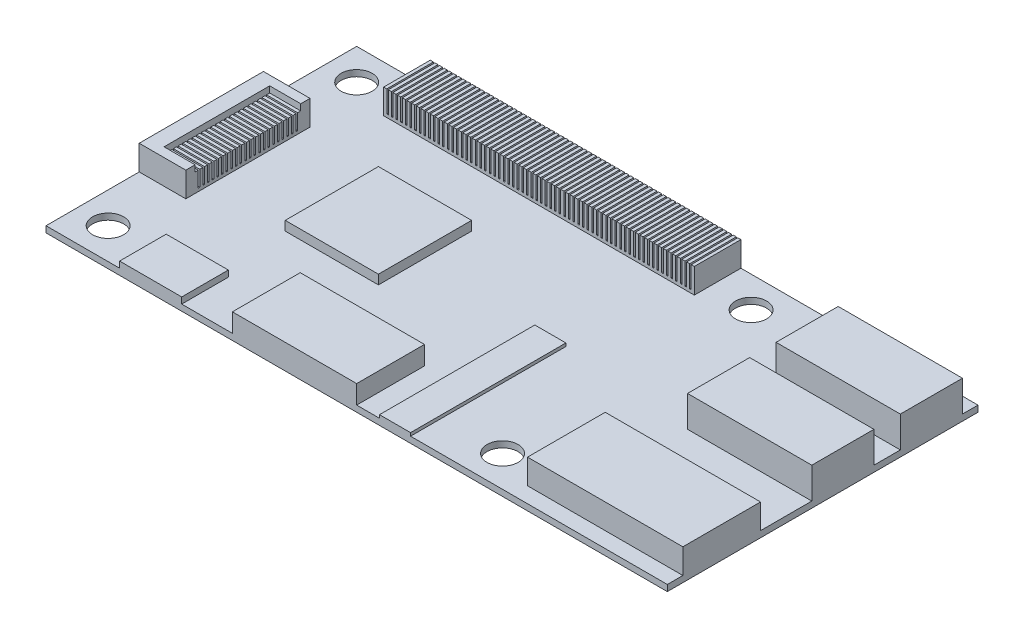
SolidWorks part; units mm, degrees
ref_plane "Front Plane" through (0, 0, 0) normal (0, 0, 1) x (1, 0, 0)
ref_plane "Top Plane" through (0, 0, 0) normal (0, 1, 0) x (1, 0, 0)
ref_plane "Right Plane" through (0, 0, 0) normal (1, 0, 0) x (0, 0, -1)
sketch "Sketch1" plane through (0, 0, 0) normal (0, 1, 0) x (1, 0, 0)
  line L1 (-10, -5) -> (10, -5)
  line L2 (-10, -5) -> (-10, 5)
  line L3 (-10, 5) -> (10, 5)
  line L4 (10, -5) -> (10, 5)
  line L5 (-10, -5) -> (10, 5) construction
  line L6 (-10, 5) -> (10, -5) construction
  line L7 (-10, 2) -> (-8.5, 2)
  line L8 (-10, 2) -> (-10, -2)
  line L9 (-10, -2) -> (-8.5, -2)
  line L10 (-8.5, 2) -> (-8.5, -2)
  line L11 (-7.631, 5) -> (2.369, 5)
  line L12 (-7.631, 5) -> (-7.631, 3.5)
  line L13 (-7.631, 3.5) -> (2.369, 3.5)
  line L14 (2.369, 5) -> (2.369, 3.5)
  line L15 (10, 4.5) -> (6, 4.5)
  line L16 (10, 4.5) -> (10, 2.5)
  line L17 (10, 2.5) -> (6, 2.5)
  line L18 (6, 4.5) -> (6, 2.5)
  line L19 (10, 1.65) -> (6, 1.65)
  line L20 (10, 1.65) -> (10, -0.35)
  line L21 (10, -0.35) -> (6, -0.35)
  line L22 (6, 1.65) -> (6, -0.35)
  line L23 (10, -2) -> (5, -2)
  line L24 (10, -2) -> (10, -4.5)
  line L25 (10, -4.5) -> (5, -4.5)
  line L26 (5, -2) -> (5, -4.5)
  line L27 (-7.631, -5) -> (-5.631, -5)
  line L28 (-7.631, -5) -> (-7.631, -3.5)
  line L29 (-7.631, -3.5) -> (-5.631, -3.5)
  line L30 (-5.631, -5) -> (-5.631, -3.5)
  line L31 (-4, -5) -> (0, -5)
  line L32 (-4, -5) -> (-4, -2.8173)
  line L33 (-4, -2.8173) -> (0, -2.8173)
  line L34 (0, -5) -> (0, -2.8173)
  line L35 (0.7346, -5) -> (1.7346, -5)
  line L36 (0.7346, -5) -> (0.7346, 0)
  line L37 (0.7346, 0) -> (1.7346, 0)
  line L38 (1.7346, -5) -> (1.7346, 0)
  line L40 (-7.481, 5) -> (-7.381, 5)
  line L42 (-7.481, 3.5) -> (-7.381, 3.5)
  circle A0 centre (-9, -4) radius 1
  circle A1 centre (-9, 4) radius 1
  circle A2 centre (3.6952, 4) radius 1
  circle A3 centre (3.6952, -4) radius 1
  circle A4 centre (-9, -4) radius 0.5
  circle A5 centre (-9, 4) radius 0.5
  circle A6 centre (3.6952, 4) radius 0.5
  circle A7 centre (3.6952, -4) radius 0.5
  point P0 (0, 0)
  dimension "D3" = 2
  dimension "D4" = 2
  dimension "D10" = 2
  dimension "D25" = 2
  dimension "D27" = 1
  dimension "D28" = 1
  dimension "D29" = 1
  dimension "D30" = 1
  dimension "D1" = 10
  dimension "D2" = 20
  dimension "D5" = 4
  dimension "D6" = 1.5
  dimension "D7" = 3
  dimension "D8" = 10
  dimension "D9" = 1.5
  dimension "D11" = 0.5
  dimension "D12" = 4
  dimension "D13" = 2
  dimension "D14" = 4
  dimension "D15" = 2
  dimension "D16" = 0.85
  dimension "D17" = 5
  dimension "D18" = 2.5
  dimension "D19" = 0.5
  dimension "D20" = 2
  dimension "D21" = 1.5
  dimension "D22" = 6
  dimension "D23" = 4
  dimension "D24" = 1
  dimension "D26" = 5
  dimension "D32" = 0.1
extrude "Boss-Extrude10" add sketch "Sketch1" against normal blind 0.2 contours L1 A3 L4 L25 L26 L23 L21 L22 L19 L17 L18 L15 L3 A2 L14 L13 L12 A1 L2 L7 L10 L9 A0 L28 L29 L30 L32 L33 L34 L36 L37 L38 | L14 L3 L12 L13 | L1 L34 L33 L32 | L1 L38 L37 L36 | L1 L30 L29 L28 | L10 L7 L2 L9 | L23 L26 L25 L4 | L19 L22 L21 L4 | L15 L18 L17 L4 | A0 L2 L1 | A1 L3 L2 | A0 | A1 | A2 | A3 region at (-6.631, 0, 4.25) region at (3.0081, 0, 3.3129) region at (4.3823, 0, -4.6871) region at (-0.4809, 0, -0.0253) region at (-9.7766, 0, 4.7766) region at (-9.6871, 0, 4.6871) region at (-2, 0, 3.9086) region at (-9.25, 0, 0) region at (1.2346, 0, 2.5) region at (-9.7766, 0, -4.7766) region at (-9.6871, 0, -4.6871) region at (-2.631, 0, -4.25) region at (7.5, 0, 3.25) region at (8, 0, -0.65) region at (8, 0, -3.5)
extrude "Boss-Extrude11" add sketch "Sketch1<5>" along normal blind 1 contours L15 L18 L17 L4 | L19 L22 L21 L4 region at (8, 0, -0.65) region at (8, 0, -3.5)
sketch "Sketch1<5>" plane through (0, 0, 0) normal (0, 1, 0) x (1, 0, 0) same geometry as "Sketch1"
extrude "Boss-Extrude12" add sketch "Sketch1<6>" along normal blind 0.8 contours L23 L26 L25 L4 region at (7.5, 0, 3.25)
sketch "Sketch1<6>" plane through (0, 0, 0) normal (0, 1, 0) x (1, 0, 0) same geometry as "Sketch1"
extrude "Boss-Extrude13" add sketch "Sketch1<7>" along normal blind 0.1 contours L14 L3 L12 L13 | L10 L7 L2 L9 | L1 L38 L37 L36 region at (-9.25, 0, 0) region at (1.2346, 0, 2.5) region at (-2.631, 0, -4.25)
sketch "Sketch1<7>" plane through (0, 0, 0) normal (0, 1, 0) x (1, 0, 0) same geometry as "Sketch1"
extrude "Boss-Extrude14" add sketch "Sketch1<8>" along normal blind 0.2 contours L1 L30 L29 L28 region at (-6.631, 0, 4.25)
sketch "Sketch1<8>" plane through (0, 0, 0) normal (0, 1, 0) x (1, 0, 0) same geometry as "Sketch1"
extrude "Boss-Extrude15" add sketch "Sketch1<9>" along normal blind 0.6 contours L1 L34 L33 L32 region at (-2, 0, 3.9086)
sketch "Sketch1<9>" plane through (0, 0, 0) normal (0, 1, 0) x (1, 0, 0) same geometry as "Sketch1"
sketch "Sketch3" plane through (0, 0.1, 0) normal (0, 1, 0) x (1, 0, 0)
  line L0 (-7.631, 3.5) -> (2.369, 3.5) construction
  line L1 (-7.631, 5) -> (-7.531, 5)
  line L2 (-7.631, 5) -> (-7.631, 3.5)
  line L3 (-7.631, 3.5) -> (-7.531, 3.5)
  line L4 (-7.531, 5) -> (-7.531, 3.5)
  line L5 (-7.631, 5) -> (2.369, 5) construction
  line L6 (-7.481, 5) -> (-7.381, 5)
  line L7 (-7.481, 5) -> (-7.481, 3.5)
  line L8 (-7.481, 3.5) -> (-7.381, 3.5)
  line L9 (-7.381, 5) -> (-7.381, 3.5)
  line L10 (-7.331, 5) -> (-7.331, 3.5)
  line L11 (-7.231, 5) -> (-7.231, 3.5)
  line L12 (-7.181, 5) -> (-7.181, 3.5)
  line L13 (-7.081, 5) -> (-7.081, 3.5)
  line L14 (-7.031, 5) -> (-7.031, 3.5)
  line L15 (-6.931, 5) -> (-6.931, 3.5)
  line L16 (-6.881, 5) -> (-6.881, 3.5)
  line L17 (-6.781, 5) -> (-6.781, 3.5)
  line L18 (-6.731, 5) -> (-6.731, 3.5)
  line L19 (-6.631, 5) -> (-6.631, 3.5)
  line L20 (-6.581, 5) -> (-6.581, 3.5)
  line L21 (-6.481, 5) -> (-6.481, 3.5)
  line L22 (-6.431, 5) -> (-6.431, 3.5)
  line L23 (-6.331, 5) -> (-6.331, 3.5)
  line L24 (-6.281, 5) -> (-6.281, 3.5)
  line L25 (-6.181, 5) -> (-6.181, 3.5)
  line L26 (-6.131, 5) -> (-6.131, 3.5)
  line L27 (-6.031, 5) -> (-6.031, 3.5)
  line L28 (-5.981, 5) -> (-5.981, 3.5)
  line L29 (-5.881, 5) -> (-5.881, 3.5)
  line L30 (-5.831, 5) -> (-5.831, 3.5)
  line L31 (-5.731, 5) -> (-5.731, 3.5)
  line L32 (-5.681, 5) -> (-5.681, 3.5)
  line L33 (-5.581, 5) -> (-5.581, 3.5)
  line L34 (-5.531, 5) -> (-5.531, 3.5)
  line L35 (-5.431, 5) -> (-5.431, 3.5)
  line L36 (-5.381, 5) -> (-5.381, 3.5)
  line L37 (-5.281, 5) -> (-5.281, 3.5)
  line L38 (-5.231, 5) -> (-5.231, 3.5)
  line L39 (-5.131, 5) -> (-5.131, 3.5)
  line L40 (-5.081, 5) -> (-5.081, 3.5)
  line L41 (-4.981, 5) -> (-4.981, 3.5)
  line L42 (-4.931, 5) -> (-4.931, 3.5)
  line L43 (-4.831, 5) -> (-4.831, 3.5)
  line L44 (-4.781, 5) -> (-4.781, 3.5)
  line L45 (-4.681, 5) -> (-4.681, 3.5)
  line L46 (-4.631, 5) -> (-4.631, 3.5)
  line L47 (-4.531, 5) -> (-4.531, 3.5)
  line L48 (-4.481, 5) -> (-4.481, 3.5)
  line L49 (-4.381, 5) -> (-4.381, 3.5)
  line L50 (-4.331, 5) -> (-4.331, 3.5)
  line L51 (-4.231, 5) -> (-4.231, 3.5)
  line L52 (-4.181, 5) -> (-4.181, 3.5)
  line L53 (-4.081, 5) -> (-4.081, 3.5)
  line L54 (-4.031, 5) -> (-4.031, 3.5)
  line L55 (-3.931, 5) -> (-3.931, 3.5)
  line L56 (-3.881, 5) -> (-3.881, 3.5)
  line L57 (-3.781, 5) -> (-3.781, 3.5)
  line L58 (-3.731, 5) -> (-3.731, 3.5)
  line L59 (-3.631, 5) -> (-3.631, 3.5)
  line L60 (-3.581, 5) -> (-3.581, 3.5)
  line L61 (-3.481, 5) -> (-3.481, 3.5)
  line L62 (-3.431, 5) -> (-3.431, 3.5)
  line L63 (-3.331, 5) -> (-3.331, 3.5)
  line L64 (-3.281, 5) -> (-3.281, 3.5)
  line L65 (-3.181, 5) -> (-3.181, 3.5)
  line L66 (-3.131, 5) -> (-3.131, 3.5)
  line L67 (-3.031, 5) -> (-3.031, 3.5)
  line L68 (-2.981, 5) -> (-2.981, 3.5)
  line L69 (-2.881, 5) -> (-2.881, 3.5)
  line L70 (-2.831, 5) -> (-2.831, 3.5)
  line L71 (-2.731, 5) -> (-2.731, 3.5)
  line L72 (-2.681, 5) -> (-2.681, 3.5)
  line L73 (-2.581, 5) -> (-2.581, 3.5)
  line L74 (-2.531, 5) -> (-2.531, 3.5)
  line L75 (-2.431, 5) -> (-2.431, 3.5)
  line L76 (-2.381, 5) -> (-2.381, 3.5)
  line L77 (-2.281, 5) -> (-2.281, 3.5)
  line L78 (-2.231, 5) -> (-2.231, 3.5)
  line L79 (-2.131, 5) -> (-2.131, 3.5)
  line L80 (-2.081, 5) -> (-2.081, 3.5)
  line L81 (-1.981, 5) -> (-1.981, 3.5)
  line L82 (-1.931, 5) -> (-1.931, 3.5)
  line L83 (-1.831, 5) -> (-1.831, 3.5)
  line L84 (-1.781, 5) -> (-1.781, 3.5)
  line L85 (-1.681, 5) -> (-1.681, 3.5)
  line L86 (-1.631, 5) -> (-1.631, 3.5)
  line L87 (-1.531, 5) -> (-1.531, 3.5)
  line L88 (-1.481, 5) -> (-1.481, 3.5)
  line L89 (-1.381, 5) -> (-1.381, 3.5)
  line L90 (-1.331, 5) -> (-1.331, 3.5)
  line L91 (-1.231, 5) -> (-1.231, 3.5)
  line L92 (-1.181, 5) -> (-1.181, 3.5)
  line L93 (-1.081, 5) -> (-1.081, 3.5)
  line L94 (-1.031, 5) -> (-1.031, 3.5)
  line L95 (-0.931, 5) -> (-0.931, 3.5)
  line L96 (-0.881, 5) -> (-0.881, 3.5)
  line L97 (-0.781, 5) -> (-0.781, 3.5)
  line L98 (-0.731, 5) -> (-0.731, 3.5)
  line L99 (-0.631, 5) -> (-0.631, 3.5)
  line L100 (-0.581, 5) -> (-0.581, 3.5)
  line L101 (-0.481, 5) -> (-0.481, 3.5)
  line L102 (-0.431, 5) -> (-0.431, 3.5)
  line L103 (-0.331, 5) -> (-0.331, 3.5)
  line L104 (-0.281, 5) -> (-0.281, 3.5)
  line L105 (-0.181, 5) -> (-0.181, 3.5)
  line L106 (-0.131, 5) -> (-0.131, 3.5)
  line L107 (-0.031, 5) -> (-0.031, 3.5)
  line L108 (0.019, 5) -> (0.019, 3.5)
  line L109 (0.119, 5) -> (0.119, 3.5)
  line L110 (0.169, 5) -> (0.169, 3.5)
  line L111 (0.269, 5) -> (0.269, 3.5)
  line L112 (0.319, 5) -> (0.319, 3.5)
  line L113 (0.419, 5) -> (0.419, 3.5)
  line L114 (0.469, 5) -> (0.469, 3.5)
  line L115 (0.569, 5) -> (0.569, 3.5)
  line L116 (0.619, 5) -> (0.619, 3.5)
  line L117 (0.719, 5) -> (0.719, 3.5)
  line L118 (0.769, 5) -> (0.769, 3.5)
  line L119 (0.869, 5) -> (0.869, 3.5)
  line L120 (0.919, 5) -> (0.919, 3.5)
  line L121 (1.019, 5) -> (1.019, 3.5)
  line L122 (1.069, 5) -> (1.069, 3.5)
  line L123 (1.169, 5) -> (1.169, 3.5)
  line L124 (1.219, 5) -> (1.219, 3.5)
  line L125 (1.319, 5) -> (1.319, 3.5)
  line L126 (1.369, 5) -> (1.369, 3.5)
  line L127 (1.469, 5) -> (1.469, 3.5)
  line L128 (1.519, 5) -> (1.519, 3.5)
  line L129 (1.619, 5) -> (1.619, 3.5)
  line L130 (1.669, 5) -> (1.669, 3.5)
  line L131 (1.769, 5) -> (1.769, 3.5)
  line L132 (1.819, 5) -> (1.819, 3.5)
  line L133 (1.919, 5) -> (1.919, 3.5)
  line L134 (1.969, 5) -> (1.969, 3.5)
  line L135 (2.069, 5) -> (2.069, 3.5)
  line L136 (2.119, 5) -> (2.119, 3.5)
  line L137 (2.219, 5) -> (2.219, 3.5)
  line L138 (2.269, 5) -> (2.269, 3.5)
  line L139 (2.369, 5) -> (2.369, 3.5)
  line M10 (2.369, 5) -> (-7.631, 5)
  line M11 (-7.631, 5) -> (-7.631, 3.5)
  line M12 (-7.631, 3.5) -> (2.369, 3.5)
  dimension "D1" = 0.1
  dimension "D2" = 0.1
  dimension "D3" = 0.05
  dimension "D4" = 66
extrude "Boss-Extrude16" add sketch "Sketch3" along normal blind 0.7 contours L4 M10 M11 M12 region at (-7.581, 0.1, -4.25)
pattern_linear "LPattern1" count 67 spacing 0.15 along (1, 0, 0) of "Boss-Extrude16"
sketch "Sketch4" plane through (0, 0.1, 0) normal (0, 1, 0) x (1, 0, 0)
  line L0 (-8.5, 1.7) -> (-9.5, 1.7)
  line L1 (-8.5, 2) -> (-8.5, -2) construction
  line L2 (-9.5, 1.7) -> (-9.5, -1.7)
  line L3 (-9.5, -1.7) -> (-8.5, -1.7)
  line L4 (-10, -2) -> (-10, 2) construction
  line L5 (-8.5, -2) -> (-8.5, -1.7)
  line L9 (-8.5, -2) -> (-8.5, 2)
  line L10 (-8.5, 2) -> (-10, 2)
  line L11 (-10, 2) -> (-10, -2)
  line L12 (-10, -2) -> (-8.5, -2)
  line L13 (-8.5, 1.7) -> (-8.5, 2)
  line L14 (-8.5, 2) -> (-10, 2)
  line L15 (-10, 2) -> (-10, -2)
  line L16 (-10, -2) -> (-8.5, -2)
  dimension "D1" = 0.3
  dimension "D2" = 0.3
  dimension "D3" = 0.5
  dimension "D4" = 0
extrude "Boss-Extrude17" add sketch "Sketch4" along normal blind 0.7
sketch "Sketch5" plane through (0, 0.1, 0) normal (0, 1, 0) x (1, 0, 0)
  line L0 (-9.5, -1.7) -> (-9.5, 1.7) construction
  line L1 (-8.5, 1.7) -> (-9.5, 1.7)
  line L2 (-8.5, 1.7) -> (-8.5, 1.6)
  line L3 (-8.5, 1.6) -> (-9.5, 1.6)
  line L4 (-9.5, 1.7) -> (-9.5, 1.6)
  dimension "D1" = 0.1
extrude "Boss-Extrude18" add sketch "Sketch5" along normal blind 0.5
pattern_linear "LPattern2" count 23 spacing 0.15 along (0, 0, 1) of "Boss-Extrude18"
sketch "Sketch6" plane through (0, 0, 0) normal (0, 1, 0) x (1, 0, 0)
  line L0 (-10, 5) -> (-7.631, 5) construction
  line L5 (-6, -1.3) -> (-3, -1.3)
  line L6 (-6, -1.3) -> (-6, 1.7)
  line L7 (-6, 1.7) -> (-3, 1.7)
  line L8 (-3, -1.3) -> (-3, 1.7)
  line L9 (-6, -1.3) -> (-3, 1.7) construction
  line L10 (-6, 1.7) -> (-3, -1.3) construction
  line L11 (-10, -5) -> (-10, -2) construction
  point P1 (-4.5, 0.2)
  point P6 (0, 0)
  dimension "D1" = 3
  dimension "D2" = 3
  dimension "D3" = 3.3
  dimension "D4" = 4
extrude "Boss-Extrude19" add sketch "Sketch6" along normal blind 0.3
sketch "Sketch8" [suppressed] plane through (0, 0.1, 0) normal (0, 1, 0) x (1, 0, 0)
  line L0 (1.7346, 0) -> (1.7346, -0.4361)
  line L1 (1.7346, -5) -> (1.7346, 0) construction
  line L2 (1.7346, -0.4361) -> (1.3346, -0.4361)
  line L3 (1.3346, -0.4361) -> (1.3346, -4.6047)
  line L4 (1.3346, -4.6047) -> (1.7346, -4.6047)
  line L5 (1.7346, -4.6047) -> (1.7346, -5)
  line L6 (1.7346, -5) -> (0.7346, -5)
  line L7 (0.7346, -5) -> (0.7346, -4.7)
  line L8 (0.7346, -5) -> (0.7346, 0) construction
  line L9 (0.7346, -4.7) -> (1.0346, -4.7)
  line L10 (1.0346, -4.7) -> (1.0346, -0.3)
  line L11 (1.0346, -0.3) -> (0.7346, -0.3)
  line L12 (0.7346, -0.3) -> (0.7346, 0)
  line L13 (0.7346, 0) -> (1.7346, 0)
  line L14 (1.7346, -5) -> (1.7346, 0) construction
  dimension "D1" = 0.3
  dimension "D2" = 0.3
  dimension "D3" = 0.4
  dimension "D4" = 0.3
extrude "Boss-Extrude20" [suppressed] add sketch "Sketch8" along normal blind 0.5
sketch "Sketch9" [suppressed] plane through (0, 0.1, 0) normal (0, 1, 0) x (1, 0, 0)
  line L0 (1.0346, -0.3) -> (1.0346, -4.7) construction
  line L1 (0.7346, -0.3) -> (1.0346, -0.3)
  line L2 (0.7346, -0.3) -> (0.7346, -0.4)
  line L3 (0.7346, -0.4) -> (1.0346, -0.4)
  line L4 (1.0346, -0.3) -> (1.0346, -0.4)
  line L5 (0.7346, -0.55) -> (1.0346, -0.55)
  line L6 (0.7346, -0.45) -> (1.0346, -0.45)
  line L7 (0.7346, -0.7) -> (1.0346, -0.7)
  line L8 (0.7346, -0.6) -> (1.0346, -0.6)
  line L9 (0.7346, -0.85) -> (1.0346, -0.85)
  line L10 (0.7346, -0.75) -> (1.0346, -0.75)
  line L11 (0.7346, -1) -> (1.0346, -1)
  line L12 (0.7346, -0.9) -> (1.0346, -0.9)
  line L13 (0.7346, -1.15) -> (1.0346, -1.15)
  line L14 (0.7346, -1.05) -> (1.0346, -1.05)
  line L15 (0.7346, -1.3) -> (1.0346, -1.3)
  line L16 (0.7346, -1.2) -> (1.0346, -1.2)
  line L17 (0.7346, -1.45) -> (1.0346, -1.45)
  line L18 (0.7346, -1.35) -> (1.0346, -1.35)
  line L19 (0.7346, -1.6) -> (1.0346, -1.6)
  line L20 (0.7346, -1.5) -> (1.0346, -1.5)
  line L21 (0.7346, -1.75) -> (1.0346, -1.75)
  line L22 (0.7346, -1.65) -> (1.0346, -1.65)
  line L23 (0.7346, -1.9) -> (1.0346, -1.9)
  line L24 (0.7346, -1.8) -> (1.0346, -1.8)
  line L25 (0.7346, -2.05) -> (1.0346, -2.05)
  line L26 (0.7346, -1.95) -> (1.0346, -1.95)
  line L27 (0.7346, -2.2) -> (1.0346, -2.2)
  line L28 (0.7346, -2.1) -> (1.0346, -2.1)
  line L29 (0.7346, -2.35) -> (1.0346, -2.35)
  line L30 (0.7346, -2.25) -> (1.0346, -2.25)
  line L31 (0.7346, -2.5) -> (1.0346, -2.5)
  line L32 (0.7346, -2.4) -> (1.0346, -2.4)
  line L33 (0.7346, -2.65) -> (1.0346, -2.65)
  line L34 (0.7346, -2.55) -> (1.0346, -2.55)
  line L35 (0.7346, -2.8) -> (1.0346, -2.8)
  line L36 (0.7346, -2.7) -> (1.0346, -2.7)
  line L37 (0.7346, -2.95) -> (1.0346, -2.95)
  line L38 (0.7346, -2.85) -> (1.0346, -2.85)
  line L39 (0.7346, -3.1) -> (1.0346, -3.1)
  line L40 (0.7346, -3) -> (1.0346, -3)
  line L41 (0.7346, -3.25) -> (1.0346, -3.25)
  line L42 (0.7346, -3.15) -> (1.0346, -3.15)
  line L43 (0.7346, -3.4) -> (1.0346, -3.4)
  line L44 (0.7346, -3.3) -> (1.0346, -3.3)
  line L45 (0.7346, -3.55) -> (1.0346, -3.55)
  line L46 (0.7346, -3.45) -> (1.0346, -3.45)
  line L47 (0.7346, -3.7) -> (1.0346, -3.7)
  line L48 (0.7346, -3.6) -> (1.0346, -3.6)
  line L49 (0.7346, -3.85) -> (1.0346, -3.85)
  line L50 (0.7346, -3.75) -> (1.0346, -3.75)
  line L51 (0.7346, -4) -> (1.0346, -4)
  line L52 (0.7346, -3.9) -> (1.0346, -3.9)
  line L53 (0.7346, -4.15) -> (1.0346, -4.15)
  line L54 (0.7346, -4.05) -> (1.0346, -4.05)
  line L55 (0.7346, -4.3) -> (1.0346, -4.3)
  line L56 (0.7346, -4.2) -> (1.0346, -4.2)
  line L57 (0.7346, -4.45) -> (1.0346, -4.45)
  line L58 (0.7346, -4.35) -> (1.0346, -4.35)
  line L59 (0.7346, -4.6) -> (1.0346, -4.6)
  line L60 (0.7346, -4.5) -> (1.0346, -4.5)
  line M5 (1.0346, -4.7) -> (1.0346, -0.3)
  line M6 (1.0346, -0.3) -> (0.7346, -0.3)
  line M7 (0.7346, -0.3) -> (0.7346, -4.7)
  dimension "D1" = 0.1
extrude "Boss-Extrude21" [suppressed] add sketch "Sketch9" along normal blind 0.4 contours L3 M7 M5 M6
pattern_linear "LPattern3" [suppressed] count 29 spacing 0.15 of bodies 114
